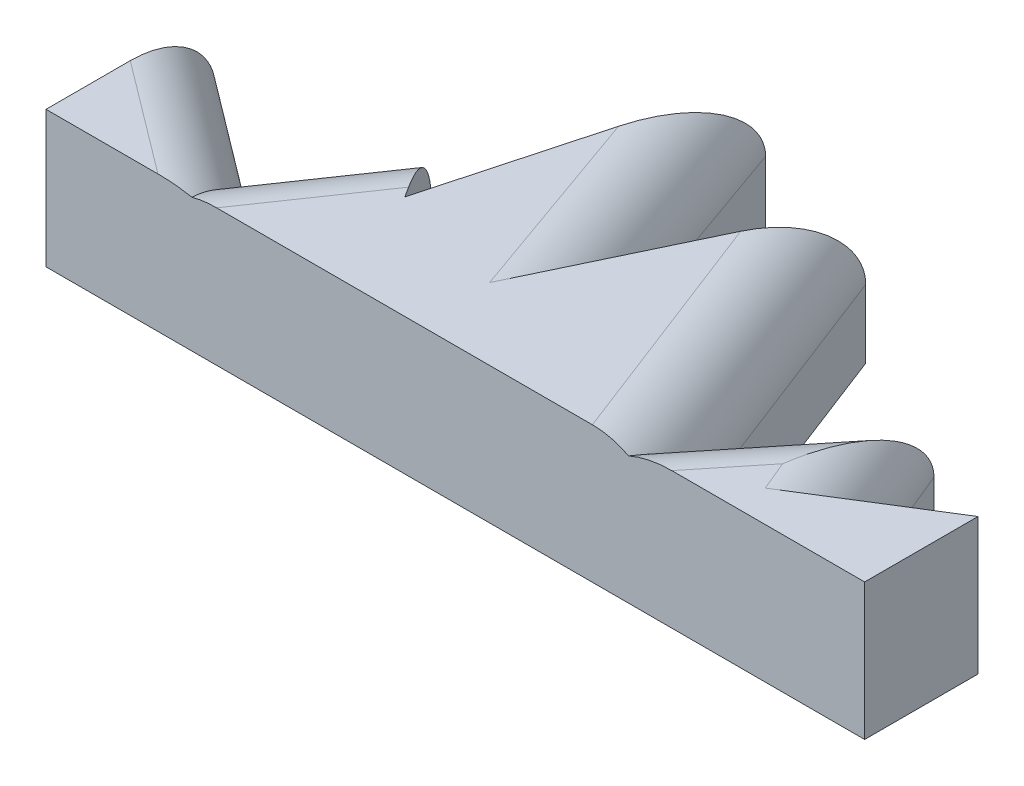
SolidWorks part; units mm, degrees
ref_plane "Front Plane" through (0, 0, 0) normal (0, 0, 1) x (1, 0, 0)
ref_plane "Top Plane" through (0, 0, 0) normal (0, 1, 0) x (1, 0, 0)
ref_plane "Right Plane" through (0, 0, 0) normal (1, 0, 0) x (0, 0, -1)
sketch "Sketch1" plane through (0, 129.5222, 0) normal (0, 1, 0) x (1, 0, 0)
  line L0 (120.0519, -70.0763) -> (120.0519, -19.2763) construction
  line L1 (-32.3481, -19.2763) -> (120.0519, -19.2763)
  line L2 (-32.3481, -19.2763) -> (-32.3481, -6.5763)
  line L3 (-32.3481, -6.5763) -> (120.0519, -6.5763)
  line L4 (120.0519, -19.2763) -> (120.0519, -6.5763)
  dimension "D1" = 12.7
extrude "Boss-Extrude1" add sketch "Sketch1" against normal up to surface (25.4 mm away)
sketch "Sketch2" plane through (0, 129.5222, 0) normal (0, 1, 0) x (1, 0, 0)
  line L0 (-32.3481, -6.5763) -> (-32.3481, 12.3121)
  line L1 (-32.3481, 12.3121) -> (-7.2688, -6.5763)
  line L2 (-7.2688, -6.5763) -> (6.5639, 13.5998)
  line L3 (6.5639, 13.5998) -> (15.1747, 0)
  line L4 (15.1747, 0) -> (29.527, 52.8111)
  line L5 (29.527, 52.8111) -> (44.6051, 10.2752)
  line L6 (44.6051, 10.2752) -> (59.494, 41.4856)
  line L7 (59.494, 41.4856) -> (78.079, -6.5763)
  line L8 (78.079, -6.5763) -> (96.9041, 16.7739)
  line L9 (96.9041, 16.7739) -> (106.5866, -6.5763)
  line L10 (106.5866, -6.5763) -> (120.0519, 1.826)
  line L11 (120.0519, 1.826) -> (120.0519, -6.5763)
  line L12 (120.0519, -6.5763) -> (-32.3481, -6.5763) construction
  line L13 (-32.3481, -6.5763) -> (-32.3481, -19.2763) construction
  line L15 (120.0519, -6.5763) -> (120.0519, -10.4966)
  line L16 (120.0519, -10.4966) -> (-32.3481, -10.4966)
  line L17 (-32.3481, -6.5763) -> (-32.3481, -10.4966)
extrude "Boss-Extrude2" add sketch "Sketch2" against normal up to surface (25.4 mm away)
fillet "Fillet1" [suppressed] radius 2.54
fillet "Fillet2" radius 12.7 6 edges at (-19.8085, 129.5222, -2.8679) (-0.3524, 129.5222, -3.5118) (101.7454, 129.5222, -5.0988) (87.4916, 129.5222, -5.0988) (68.7865, 129.5222, -17.4547) (37.066, 129.5222, -31.5431)
